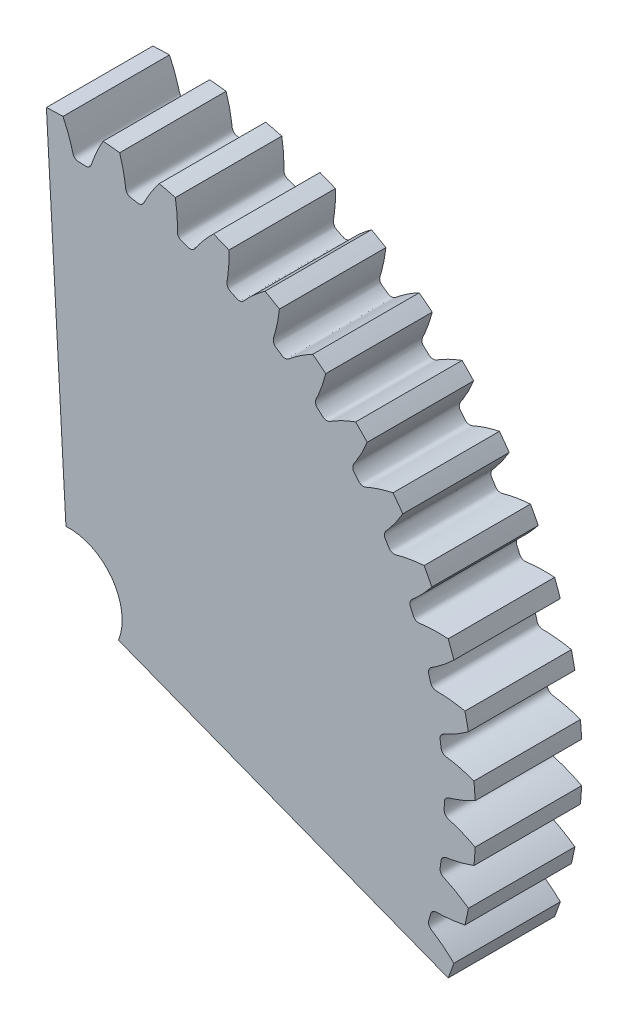
SolidWorks part; units mm, degrees
ref_plane "Front Plane" through (0, 0, 0) normal (0, 0, 1) x (1, 0, 0)
ref_plane "Top Plane" through (0, 0, 0) normal (0, 1, 0) x (1, 0, 0)
ref_plane "Right Plane" through (0, 0, 0) normal (1, 0, 0) x (0, 0, -1)
ref_axis "Axis1" through (0, 0, 4.4) along (0, 0, -1)
sketch "SketchRevolveGeartrax1Pinion" plane through (0, 0, 0) normal (1, 0, 0) x (0, 0, -1)
  line L0 (0, 0) -> (1, 0) construction
  line L1 (-4, 0) -> (-4, 30.5649)
  line L2 (-4, 30.5649) -> (4, 30.5649)
  line L3 (4, 30.5649) -> (4, 0)
  line L4 (4, 0) -> (-4, 0)
  dimension "Side1" = 4
  dimension "OutsideRadius" = 30.5649
  dimension "Side2" = 4
revolve "Geartrax1Pinion" add sketch "SketchRevolveGeartrax1Pinion" angle 360 about L0
sketch "SketchToothGeartrax1Pinion" plane through (0, 0, 0) normal (0, 0, 1) x (1, 0, 0)
  arc A0 (30.5788, 1.5364) -> (30.5788, -1.5364) centre (0, 0) cw
  spline S0 degree 3 poles (30.5788, -1.5364) (30.493, -1.4909) (30.365, -1.4248) (30.1951, -1.3409) (30.072, -1.2819) (29.9515, -1.2258) (29.8338, -1.1726) (29.7188, -1.1222) (29.6066, -1.0746) (29.4973, -1.0297) (29.3909, -0.9875) (29.2875, -0.9478) (29.1871, -0.9105) (29.0897, -0.8757) (28.9954, -0.8432) (28.9043, -0.8129) (28.8162, -0.7849) (28.6976, -0.7479) (28.5965, -0.7227) (28.5166, -0.6929) (28.4864, -0.68) (28.4551, -0.6647) (28.4223, -0.6461) (28.3874, -0.6228) (28.35, -0.5928) (28.3104, -0.5535) (28.2703, -0.5015) (28.234, -0.4341) (28.2081, -0.3532) (28.1971, -0.206) (28.2087, 0) (28.1971, 0.206) (28.2081, 0.3532) (28.234, 0.4341) (28.2703, 0.5015) (28.3104, 0.5535) (28.35, 0.5928) (28.3874, 0.6228) (28.4223, 0.6461) (28.4551, 0.6647) (28.4864, 0.68) (28.5166, 0.6929) (28.5965, 0.7227) (28.6976, 0.7479) (28.8162, 0.7849) (28.9043, 0.8129) (28.9954, 0.8432) (29.0897, 0.8757) (29.1871, 0.9105) (29.2875, 0.9478) (29.3909, 0.9875) (29.4973, 1.0297) (29.6066, 1.0746) (29.7188, 1.1222) (29.8338, 1.1726) (29.9515, 1.2258) (30.072, 1.2819) (30.1951, 1.3409) (30.365, 1.4248) (30.493, 1.4909) (30.5788, 1.5364) knots 0 0 0 0 0.047616 0.070521 0.092825 0.114526 0.135626 0.156124 0.176021 0.195315 0.214008 0.232099 0.249588 0.266475 0.282761 0.298445 0.313527 0.328007 0.359335 0.364462 0.369782 0.37541 0.381501 0.38826 0.395957 0.404923 0.415516 0.427998 0.442292 0.456735 0.5 0.543265 0.557708 0.572002 0.584484 0.595077 0.604043 0.61174 0.618499 0.62459 0.630218 0.635538 0.640665 0.671993 0.686473 0.701555 0.717239 0.733525 0.750412 0.767901 0.785992 0.804685 0.823979 0.843876 0.864374 0.885474 0.907175 0.929479 0.952384 1 1 1 1
extrude "ToothExtrudeCutGeartrax1Pinion" cut sketch "SketchToothGeartrax1Pinion" against normal blind 4 and the other way blind 4
pattern_circular "PatternGeartrax1Pinion" count 45 every 8 about axis through (0, 0, 4.4) along (0, 0, -1) of "ToothExtrudeCutGeartrax1Pinion"
sketch "BoreRevolveSketch" plane through (0, 0, 0) normal (1, 0, 0) x (0, 0, -1)
  line L0 (0, 0) -> (1, 0) construction
  line L1 (-4, 0) -> (4, 0)
  line L2 (4, 0) -> (4, 4)
  line L3 (4, 4) -> (-4, 4)
  line L4 (-4, 4) -> (-4, 0)
  dimension "BoreSide1" = 4
  dimension "TaperSide1" = 4
  dimension "BoreSide2" = 4
  dimension "TaperSide2" = 4
revolve "BoreRevolveCut" cut sketch "BoreRevolveSketch" angle 360 about L0
sketch "AuxiliarySketchGeartrax1Pinion" plane through (0, 0, 0) normal (0, 0, 1) x (1, 0, 0)
  circle A0 centre (0, 0) radius 29.5155 construction
  circle A1 centre (0, 0) radius 27.7355 construction
  circle A2 centre (0, 0) radius 28.6093 construction
  circle A3 centre (0, 0) radius 30.5649 construction
  circle A4 centre (0, 0) radius 28.2037 construction
  dimension "PitchDiameter" = 59.031
  dimension "BaseDiameter" = 55.471
  dimension "FormDiameter" = 57.2185
  dimension "MajorDiameter" = 61.1299
  dimension "MinorDiameter" = 56.4074
sketch "Sketch6" plane through (0, 0, 4) normal (0, 0, 1) x (1, 0, 0)
  line L0 (0, 0) -> (-1.6899, 30.5182)
  line L1 (0, 0) -> (28.5023, -11.0378)
  arc A0 (28.5023, -11.0378) -> (-1.6899, 30.5182) centre (0, 0) ccw
  point P7 (0, 0)
  point P8 (0, 0)
extrude "Cut-Extrude2" cut sketch "Sketch6" against normal through all flip side to cut
